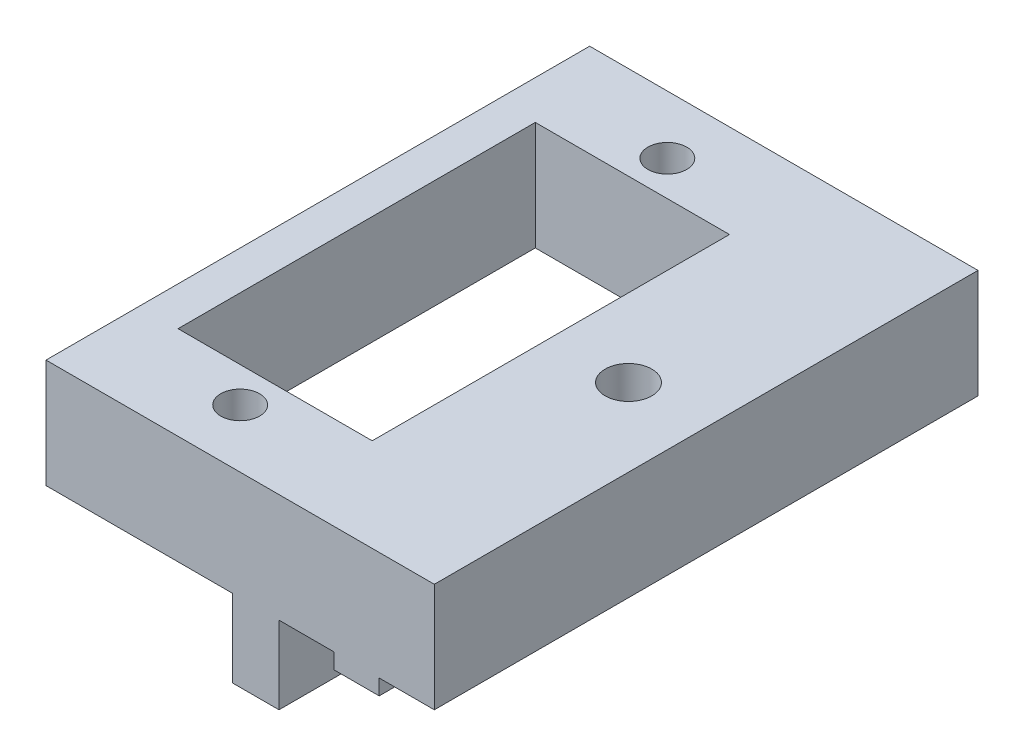
SolidWorks part; units mm, degrees
ref_plane "Front Plane" through (0, 0, 0) normal (0, 0, 1) x (1, 0, 0)
ref_plane "Top Plane" through (0, 0, 0) normal (0, 1, 0) x (1, 0, 0)
ref_plane "Right Plane" through (0, 0, 0) normal (1, 0, 0) x (0, 0, -1)
sketch "Sketch1" plane through (0, 0, 0) normal (0, 0, 1) x (1, 0, 0)
  line L0 (10, 0) -> (10, 7)
  line L1 (10, 7) -> (-15, 7)
  line L2 (-15, 7) -> (-15, 0)
  line L3 (-15, 0) -> (-3, 0)
  line L4 (3.55, 0) -> (3.55, -1)
  line L5 (3.55, -1) -> (6.45, -1)
  line L6 (6.45, -1) -> (6.45, 0)
  line L7 (6.45, 0) -> (10, 0)
  line L8 (-3, 0) -> (-3, -5)
  line L9 (-3, -5) -> (0, -5)
  line L10 (0, -5) -> (0, 0)
  line L11 (0, 0) -> (3.55, 0)
  dimension "D1" = 10
  dimension "D2" = 1
  dimension "D3" = 7
  dimension "D4" = 2.9
  dimension "D5" = 3.55
  dimension "D6" = 15
  dimension "D7" = 3
  dimension "D8" = 5
extrude "Main" add sketch "Sketch1" along normal mid plane 35
sketch "Sketch2" plane through (0, 7, 0) normal (0, 1, 0) x (1, 0, 0)
  line L0 (10, -17.5) -> (10, 17.5) construction
  line L1 (-6.25, -13.75) -> (-6.25, 13.75) construction
  circle A0 centre (5, 0) radius 1.5
  circle A1 centre (-6.25, 13.75) radius 1.25
  circle A2 centre (-6.25, -13.75) radius 1.25
  point P9 (-6.25, 0)
  dimension "D1" = 3
  dimension "D3" = 2.5
  dimension "D2" = 5
  dimension "D4" = 6.25
  dimension "D5" = 27.5
extrude "FixingHole" cut sketch "Sketch2" against normal through all
sketch "Sketch3" plane through (0, 7, 0) normal (0, 1, 0) x (1, 0, 0)
  line L1 (-12.5, 11.5) -> (0, 11.5)
  line L2 (-12.5, 11.5) -> (-12.5, -11.5)
  line L3 (-12.5, -11.5) -> (0, -11.5)
  line L4 (0, 11.5) -> (0, -11.5)
  point P6 (0, 0)
  dimension "D1" = 23
  dimension "D2" = 12.5
extrude "ServoSquareHole" cut sketch "Sketch3" against normal through all
